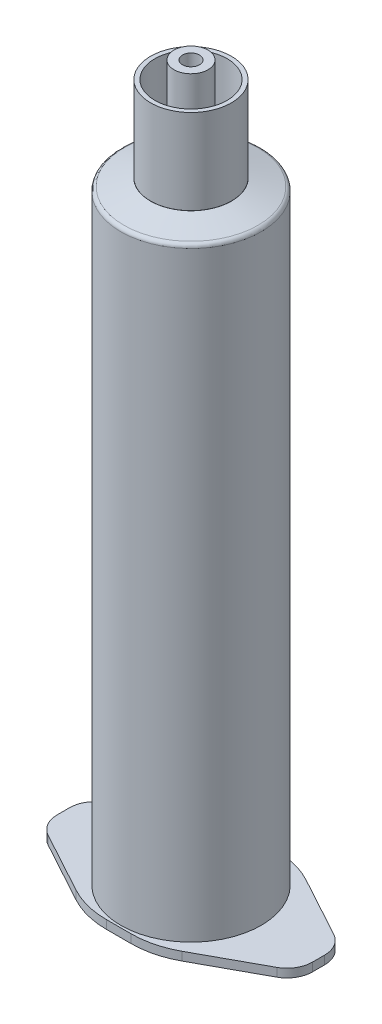
SolidWorks part; units mm, degrees
ref_plane "Front Plane" through (0, 0, 0) normal (0, 0, 1) x (1, 0, 0)
ref_plane "Top Plane" through (0, 0, 0) normal (0, 1, 0) x (1, 0, 0)
ref_plane "Right Plane" through (0, 0, 0) normal (1, 0, 0) x (0, 0, -1)
sketch "Sketch1" plane through (0, 0, 0) normal (0, 1, 0) x (1, 0, 0)
  circle A0 centre (0, 0) radius 6.5 construction
  circle A1 centre (0, 0) radius 8.25
  dimension "D1" = 13
  dimension "D2" = 16.5
extrude "Boss-Extrude1" add sketch "Sketch1" along normal blind 85
sketch "Sketch2" plane through (0, 85, 0) normal (0, 1, 0) x (1, 0, 0)
  circle A0 centre (0, 0) radius 2
  dimension "D1" = 4
extrude "Cut-Extrude1" cut sketch "Sketch2" against normal blind 12 flip side to cut
sketch "Sketch3" plane through (0, 73, 0) normal (0, 1, 0) x (1, 0, 0)
  circle A0 centre (0, 0) radius 4.25
  circle A1 centre (0, 0) radius 4.75
  dimension "D1" = 9.5
  dimension "D2" = 8.5
extrude "Boss-Extrude2" add sketch "Sketch3" along normal offset from surface (10 mm away) 2 up to face at (0, 85, 2)
chamfer "Chamfer1" distance 1 angle 74 1 edges at (0, 73, 8.25) first distance on face at (0, 0, 8.25)
fillet "Fillet1" radius 0.5 1 edges at (0, 72, 8.25)
shell "Shell1" thickness 1 removed face at (0, 85, 2) removed face at (0, 0, 8.25)
sketch "Sketch4" plane through (0, 0, 0) normal (0, -1, 0) x (1, 0, 0)
  line L0 (-13.4366, 3.3528) -> (-6.2386, 7.279)
  line L2 (6.2386, 7.279) -> (13.4366, 3.3528)
  line L3 (15, 0.7191) -> (15, -0.7191)
  line L4 (13.4366, -3.3528) -> (6.2386, -7.279)
  line L5 (1.4501, -8.5) -> (-1.4501, -8.5)
  line L6 (-6.2386, -7.279) -> (-13.4366, -3.3528)
  line L7 (-15, -0.7191) -> (-15, 0.7191)
  line L8 (-1.4501, 8.5) -> (1.4501, 8.5)
  arc A0 (-6.2386, 7.279) -> (-1.4501, 8.5) centre (-1.4501, -1.5) cw
  arc A1 (1.4501, 8.5) -> (6.2386, 7.279) centre (1.4501, -1.5) cw
  arc A2 (-1.4501, -8.5) -> (-6.2386, -7.279) centre (-1.4501, 1.5) cw
  arc A3 (6.2386, -7.279) -> (1.4501, -8.5) centre (1.4501, 1.5) cw
  arc A4 (13.4366, 3.3528) -> (15, 0.7191) centre (12, 0.7191) cw
  arc A5 (15, -0.7191) -> (13.4366, -3.3528) centre (12, -0.7191) cw
  arc A6 (-13.4366, 3.3528) -> (-15, 0.7191) centre (-12, 0.7191) ccw
  arc A7 (-13.4366, -3.3528) -> (-15, -0.7191) centre (-12, -0.7191) cw
  circle A8 centre (0, 0) radius 7.25
  circle A9 centre (0, 0) radius 7.25 construction
  point P5 (0, -8.5)
  point P9 (0, 8.5)
  point P11 (-15, 0)
  point P12 (15, 0)
  point P20 (-4, 8.5)
  point P23 (4, 8.5)
  point P34 (-15, 2.5)
  point P37 (-15, -2.5)
  dimension "D5" = 10
  dimension "D6" = 3
  dimension "D7" = 3
  dimension "D1" = 30
  dimension "D2" = 8.5
  dimension "D3" = 8
  dimension "D4" = 5
extrude "Boss-Extrude3" add sketch "Sketch4" against normal blind 1
sketch "Sketch5" plane through (0, 72, 0) normal (0, 1, 0) x (1, 0, 0)
  point P0 (0, 0)
